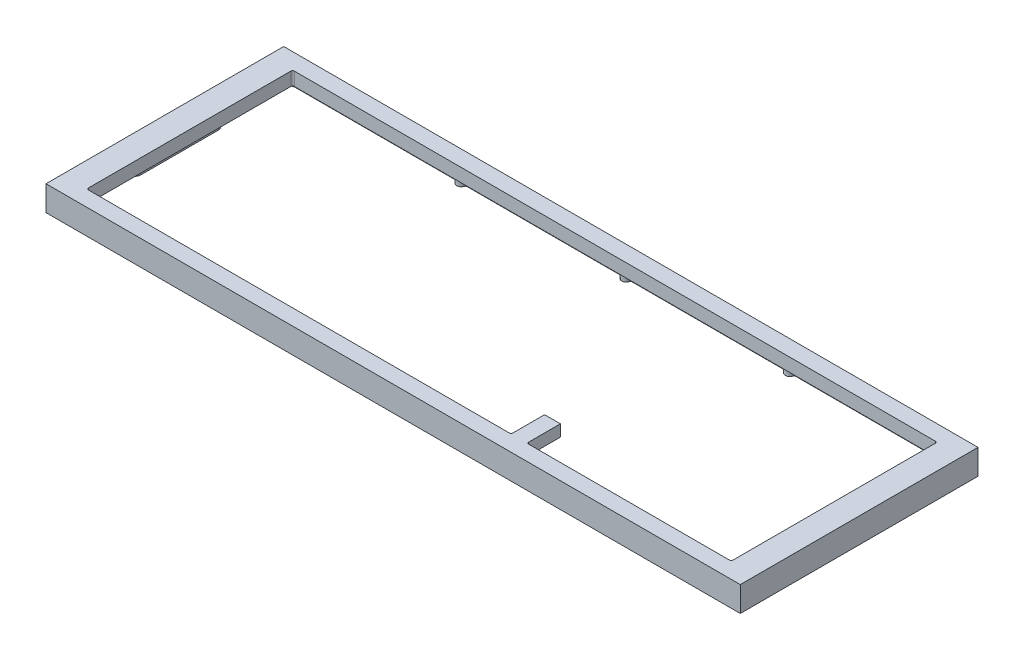
SolidWorks part; units mm, degrees
material "6061 Alloy"
ref_plane "Front Plane" through (0, 0, 0) normal (0, 0, 1) x (1, 0, 0)
ref_plane "Top Plane" through (0, 0, 0) normal (0, 1, 0) x (1, 0, 0)
ref_plane "Right Plane" through (0, 0, 0) normal (1, 0, 0) x (0, 0, -1)
sketch "Sketch1" plane through (0, 0, 0) normal (0, 1, 0) x (1, 0, 0)
  line L1 (0, 0) -> (390.8, 0)
  line L2 (0, 0) -> (0, -133.8)
  line L3 (0, -133.8) -> (390.8, -133.8)
  line L4 (390.8, 0) -> (390.8, -133.8)
  dimension "D1" = 390.8
  dimension "D2" = 133.8
extrude "Boss-Extrude1" add sketch "Sketch1" along normal blind 14.1
sketch "Sketch2" plane through (0, 14.1, 0) normal (0, 1, 0) x (1, 0, 0)
  line L0 (390.8, 0) -> (0, 0) construction
  line L1 (14, -9) -> (376.8, -9)
  line L2 (14, -9) -> (14, -124.9)
  line L3 (14, -124.9) -> (376.8, -124.9)
  line L4 (376.8, -9) -> (376.8, -124.9)
  line L5 (0, -133.8) -> (390.8, -133.8) construction
  line L6 (0, 0) -> (0, -133.8) construction
  line L7 (390.8, -133.8) -> (390.8, 0) construction
  line L8 (390.8, -133.8) -> (390.8, 0) construction
  line L9 (261.8, -124.9) -> (252.9, -124.9)
  line L10 (261.8, -124.9) -> (261.8, -106.05)
  line L11 (261.8, -106.05) -> (252.9, -106.05)
  line L12 (252.9, -124.9) -> (252.9, -106.05)
  line L13 (0, -133.8) -> (390.8, -133.8) construction
  dimension "D1" = 9
  dimension "D2" = 8.9
  dimension "D3" = 14
  dimension "D4" = 14
  dimension "D5" = 129
  dimension "D6" = 137.9
  dimension "D7" = 27.75
extrude "Cut-Extrude1" cut sketch "Sketch2" against normal through all contours L3 L12 L11 L10 L4 L1 L2 region at (195.1518, 14.1, 66.7556)
sketch "Sketch3" plane through (0, 0, 0) normal (0, -1, 0) x (1, 0, 0)
  line L0 (390.8, 0) -> (0, 0) construction
  line L1 (385.5, 2.6) -> (5.3, 2.6)
  line L2 (385.5, 2.6) -> (385.5, 131.2)
  line L3 (385.5, 131.2) -> (5.3, 131.2)
  line L4 (5.3, 2.6) -> (5.3, 131.2)
  line L5 (390.8, 133.8) -> (390.8, 0) construction
  point P4 (195.4, 2.6)
  point P7 (195.4, 0)
  point P8 (385.5, 66.9)
  point P11 (390.8, 66.9)
  dimension "D1" = 380.2
  dimension "D2" = 128.6
extrude "Cut-Extrude2" cut sketch "Sketch3" against normal blind 6.6 contours L2 L1 L4 L3
sketch "Sketch5" plane through (0, 6.6, 0) normal (0, -1, 0) x (1, 0, 0)
  line L0 (290, 128.2) -> (285, 128.2)
  line L1 (290, 128.2) -> (290, 131.2)
  line L2 (290, 131.2) -> (285, 131.2)
  line L3 (285, 128.2) -> (285, 131.2)
  line L4 (105, 128.2) -> (100, 128.2)
  line L5 (105, 128.2) -> (105, 131.2)
  line L6 (105, 131.2) -> (100, 131.2)
  line L7 (100, 128.2) -> (100, 131.2)
  line L8 (8.3, 45) -> (8.3, 88.8)
  line L9 (382.5, 45) -> (382.5, 88.8)
  line L10 (0, 133.8) -> (390.8, 133.8) construction
  line L11 (5.3, 2.6) -> (5.3, 131.2) construction
  line L12 (390.8, 0) -> (0, 0) construction
  line L13 (385.5, 2.6) -> (385.5, 131.2) construction
  line L15 (385.5, 131.2) -> (5.3, 131.2) construction
  line L16 (385.5, 131.2) -> (5.3, 131.2) construction
  line L17 (385.5, 2.6) -> (5.3, 2.6) construction
  line L18 (5.3, 2.6) -> (5.3, 131.2) construction
  circle A0 centre (102.5, 128.2) radius 2.5
  circle A1 centre (287.5, 128.2) radius 2.5
  circle A2 centre (102.5, 2.6) radius 2.5
  circle A3 centre (195.4, 2.6) radius 2.5
  circle A4 centre (287.5, 2.6) radius 2.5
  circle A5 centre (385.5, 45) radius 3
  circle A6 centre (385.5, 88.8) radius 3
  circle A7 centre (5.3, 45) radius 3
  circle A8 centre (5.3, 88.8) radius 3
  point P26 (0, 0)
  point P35 (0, 0)
  point P38 (0, 0)
  line M9 (5.3, 131.2) -> (5.3, 2.6)
  line M10 (5.3, 2.6) -> (385.5, 2.6)
  line M11 (385.5, 2.6) -> (385.5, 131.2)
  dimension "D1" = 5
  dimension "D5" = 6
  dimension "D2" = 185
  dimension "D3" = 92.9
  dimension "D4" = 185
  dimension "D6" = 45
  dimension "D7" = 97.2
  dimension "D8" = 3
  dimension "D9" = 97.2
  dimension "D10" = 45
  dimension "D11" = 45
extrude "Boss-Extrude2" add sketch "Sketch5" along normal up to surface (6.6 mm away) contours A6 L9 A5 M11 | A5 M11 | A6 M11 | A4 M10 | A3 M10 | A2 M10 | A7 M9 | A8 A7 L8 M9 | A8 M9 | A0 | L7 L6 L5 L4 | L3 L2 L1 L0 | A1 region at (6.8273, 6.6, 66.9) region at (6.5732, 6.6, 45) region at (384.2268, 6.6, 45) region at (287.5, 6.6, 3.661) region at (195.4, 6.6, 3.661) region at (102.5, 6.6, 3.661) region at (6.5732, 6.6, 88.8) region at (383.9727, 6.6, 66.9) region at (384.2268, 6.6, 88.8) up to face at (195.4, 0, 66.9)
sketch "Sketch6" plane through (0, 6.6, 0) normal (0, -1, 0) x (-1, 0, 0)
  line L0 (-195.4, 0) -> (-195.4, -133.8) construction
  line L1 (-390.8, 0) -> (0, 0) construction
  line L2 (0, -133.8) -> (-390.8, -133.8) construction
  line L3 (-390.8, -66.9) -> (0, -66.9) construction
  line L4 (-390.8, -133.8) -> (-390.8, 0) construction
  line L5 (0, 0) -> (0, -133.8) construction
  point P12 (-382.9, -22.7)
  point P13 (-382.9, -111)
  point P14 (-325.4, -129)
  point P15 (-195.4, -129)
  point P16 (0, 0)
  point P17 (0, 0)
  point P18 (-65.4, -129)
  point P19 (-7.9, -111)
  point P20 (-7.9, -22.7)
  dimension "D1" = 22.8
  dimension "D2" = 22.7
  dimension "D3" = 7.9
  dimension "D4" = 65.4
  dimension "D5" = 4.8
sketch "Sketch7" plane through (0, 0, 0) normal (0, -1, 0) x (1, 0, 0)
  arc A0 (382.5, 45) -> (385.5, 42) centre (385.5, 45) ccw construction
  arc A1 (385.5, 91.8) -> (382.5, 88.8) centre (385.5, 88.8) ccw construction
  arc A2 (290, 2.6) -> (285, 2.6) centre (287.5, 2.6) ccw construction
  arc A3 (197.9, 2.6) -> (192.9, 2.6) centre (195.4, 2.6) ccw construction
  arc A4 (105, 2.6) -> (100, 2.6) centre (102.5, 2.6) ccw construction
  arc A5 (5.3, 42) -> (8.3, 45) centre (5.3, 45) ccw construction
  arc A6 (8.3, 88.8) -> (5.3, 91.8) centre (5.3, 88.8) ccw construction
  arc A7 (100, 128.2) -> (105, 128.2) centre (102.5, 128.2) ccw construction
  arc A8 (285, 128.2) -> (290, 128.2) centre (287.5, 128.2) ccw construction
  point P0 (385.5, 45)
  point P1 (385.5, 88.8)
  point P2 (287.5, 128.2)
  point P3 (102.5, 128.2)
  point P4 (5.3, 88.8)
  point P5 (5.3, 45)
  point P6 (102.5, 2.6)
  point P7 (195.4, 2.6)
  point P8 (287.5, 2.6)
  point P10 (0, 0)
  point P15 (0, 0)
  point P19 (0, 0)
  point P23 (0, 0)
  point P27 (0, 0)
  point P31 (0, 0)
  point P32 (0, 0)
  point P36 (0, 0)
  point P40 (0, 0)
  point P44 (0, 0)
sketch "Sketch8" plane through (0, 6.6, 0) normal (0, -1, 0) x (1, 0, 0)
  line L1 (261.8, 106.05) -> (252.9, 106.05)
  line L2 (261.8, 106.05) -> (261.8, 124.9)
  line L3 (261.8, 124.9) -> (252.9, 124.9)
  line L4 (252.9, 106.05) -> (252.9, 124.9)
extrude "Cut-Extrude3" cut sketch "Sketch8" against normal blind 1
hole_wizard "M2x0.4 Tapped Hole1" positions "3DSketch2" profile "Sketch10" tap size "M2x0.4" standard "ANSI Metric"
sketch3d "3DSketch2"
  point P0 (385.5, 0, 45)
  point P3 (385.5, 0, 88.8)
  point P6 (287.5, 0, 128.2)
  point P9 (102.5, 0, 128.2)
  point P12 (5.3, 0, 88.8)
  point P15 (5.3, 0, 45)
  point P18 (102.5, 0, 2.6)
  point P21 (287.5, 0, 2.6)
  point P24 (195.4, 0, 2.6)
sketch "Sketch10" plane through (385.5, 0, 45) normal (1, 0, 0) x (0, 0, -1)
  line L0 (0, 0) -> (0, 11.4807)
  line L1 (0, 11.4807) -> (0.8, 11)
  line L2 (0.8, 11) -> (0.8, 0)
  line L5 (0.8, 0) -> (0, 0)
  line L10 (0, 11.4807) -> (-0.8, 11) construction
  line L11 (0, -6.35) -> (0, 107.95) construction
  dimension "Tap Drill Dia." = 1.6
  dimension "Tap Drill Depth" = 11
  dimension "Drill Angle" = 118
cosmetic thread "Hole Thread1" parameters "D1"=4, "D2"=2
cosmetic thread "Hole Thread2" parameters "D1"=4, "D2"=2
cosmetic thread "Hole Thread3" parameters "D1"=4, "D2"=2
cosmetic thread "Hole Thread4" parameters "D1"=4, "D2"=2
cosmetic thread "Hole Thread5" parameters "D1"=4, "D2"=2
cosmetic thread "Hole Thread6" parameters "D1"=4, "D2"=2
cosmetic thread "Hole Thread7" parameters "D1"=4, "D2"=2
cosmetic thread "Hole Thread8" parameters "D1"=4, "D2"=2
cosmetic thread "Hole Thread9" parameters "D1"=4, "D2"=2
hole_wizard "M2x0.4 Tapped Hole2" positions "3DSketch3" profile "Sketch11" tap size "M2x0.4" standard "ANSI Metric"
sketch3d "3DSketch3"
  point P0 (382.9, 6.6, 22.7)
  point P3 (382.9, 6.6, 111)
  point P6 (325.4, 6.6, 129)
  point P9 (195.4, 6.6, 129)
  point P12 (65.4, 6.6, 129)
  point P15 (7.9, 6.6, 22.7)
  point P18 (7.9, 6.6, 111)
sketch "Sketch11" plane through (382.9, 6.6, 22.7) normal (1, 0, 0) x (0, 0, -1)
  line L0 (0, 0) -> (0, 4.9807)
  line L1 (0, 4.9807) -> (0.8, 4.5)
  line L2 (0.8, 4.5) -> (0.8, 0)
  line L5 (0.8, 0) -> (0, 0)
  line L10 (0, 4.9807) -> (-0.8, 4.5) construction
  line L11 (0, -6.35) -> (0, 107.95) construction
  dimension "Tap Drill Dia." = 1.6
  dimension "Tap Drill Depth" = 4.5
  dimension "Drill Angle" = 118
cosmetic thread "Hole Thread10" parameters "D1"=4, "D2"=2
cosmetic thread "Hole Thread11" parameters "D1"=4, "D2"=2
cosmetic thread "Hole Thread12" parameters "D1"=4, "D2"=2
cosmetic thread "Hole Thread13" parameters "D1"=4, "D2"=2
cosmetic thread "Hole Thread14" parameters "D1"=4, "D2"=2
cosmetic thread "Hole Thread15" parameters "D1"=4, "D2"=2
cosmetic thread "Hole Thread16" parameters "D1"=4, "D2"=2
fillet "Fillet1" radius 4 12 edges at (385.5, 3.3, 42) (385.5, 3.3, 2.6) (5.3, 3.3, 2.6) (5.3, 3.3, 42) (5.3, 3.3, 91.8) (5.3, 3.3, 131.2) (100, 3.3, 131.2) (105, 3.3, 131.2) (290, 3.3, 131.2) (285, 3.3, 131.2) (385.5, 3.3, 131.2) (385.5, 3.3, 91.8)
fillet "Fillet2" radius 1 12 edges at (376.8, 10.35, 9) (376.8, 10.35, 124.9) (14, 10.35, 124.9) (14, 10.35, 9) (105, 3.3, 2.6) (100, 3.3, 2.6) (197.9, 3.3, 2.6) (192.9, 3.3, 2.6) (285, 3.3, 2.6) (290, 3.3, 2.6) (261.8, 10.85, 124.9) (252.9, 10.85, 124.9)
sketch "Sketch12" plane through (0, 0, 0) normal (0, -1, 0) x (1, 0, 0)
  line L0 (390.8, 0) -> (0, 0) construction
  line L1 (41.8819, 0) -> (26.6819, 0)
  line L2 (41.8819, 0) -> (41.8819, 2)
  line L3 (41.8819, 2) -> (26.6819, 2)
  line L4 (26.6819, 0) -> (26.6819, 2)
  line L5 (0, 0) -> (0, 133.8) construction
  dimension "D1" = 2
  dimension "D2" = 15.2
  dimension "D3" = 26.6819
extrude "Cut-Extrude4" cut sketch "Sketch12" against normal blind 2
fillet "Fillet3" radius 4 2 edges at (26.6819, 1, 2) (41.8819, 1, 2)
